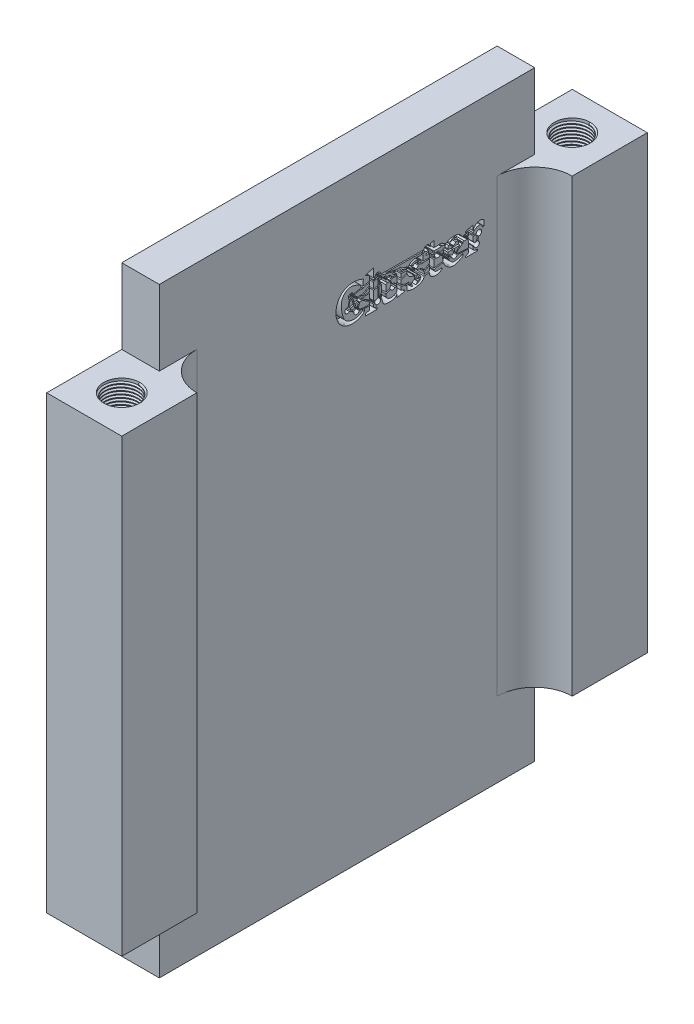
SolidWorks part; units mm, degrees
material "Polylactic Acid (PLA)"
ref_plane "Front Plane" through (0, 0, 0) normal (0, 0, 1) x (1, 0, 0)
ref_plane "Top Plane" through (0, 0, 0) normal (0, 1, 0) x (1, 0, 0)
ref_plane "Right Plane" through (0, 0, 0) normal (1, 0, 0) x (0, 0, -1)
sketch "Sketch2" plane through (0, 0, 0) normal (1, 0, 0) x (0, 0, -1)
  line L0 (-25, 40) -> (25, 40)
  line L1 (-25, 40) -> (-25, 30)
  line L2 (-25, -40) -> (25, -40)
  line L3 (25, 30) -> (35, 30)
  line L4 (25, 40) -> (25, 30)
  line L5 (35, 30) -> (35, -30)
  line L7 (25, -40) -> (25, -30)
  line L8 (25, -30) -> (35, -30)
  line L12 (-25, 30) -> (-35, 30)
  line L13 (-35, 30) -> (-35, -30)
  line L18 (-35, -30) -> (-25, -30)
  line L19 (-25, -30) -> (-25, -40)
extrude "Boss-Extrude1" add sketch "Sketch2" along normal blind 5
sketch "Sketch3" plane through (5, 0, 0) normal (1, 0, 0) x (0, 0, -1)
  line L1 (-35, 30) -> (-25, 30)
  line L2 (-35, 30) -> (-35, -30)
  line L3 (-35, -30) -> (-25, -30)
  line L4 (-25, 30) -> (-25, -30)
  line L5 (25, 30) -> (35, 30)
  line L6 (25, 30) -> (25, -30)
  line L7 (25, -30) -> (35, -30)
  line L8 (35, 30) -> (35, -30)
extrude "Boss-Extrude2" add sketch "Sketch3" along normal blind 5
fillet "Fillet1" radius 5 2 edges at (5, 0, -25) (5, 0, 25)
sketch "Sketch4" plane through (0, -30, 0) normal (0, -1, 0) x (1, 0, 0)
  line L0 (10, 30) -> (0, 30) construction
  line L3 (10, 35) -> (10, 25) construction
  line L5 (0, 35) -> (0, 25) construction
  line L8 (5, 35) -> (5, 25) construction
  line L10 (10, 35) -> (0, 35) construction
  line L11 (10, -30) -> (0, -30) construction
  line L12 (10, -25) -> (10, -35) construction
  line L13 (0, -25) -> (0, -35) construction
  line L14 (5, -35) -> (5, -25) construction
  line L15 (10, -35) -> (0, -35) construction
  circle A0 centre (5, 30) radius 2.4
  circle A1 centre (5, -30) radius 2.4
extrude "Cut-Extrude1" cut sketch "Sketch4" against normal blind 100
sketch "Sketch5" plane through (5, 0, 0) normal (1, 0, 0) x (0, 0, -1)
  line L2 (-1.6758, 24.7708) -> (8.3242, 24.7708) construction
  line L3 (2.4536, 27.3276) -> (3.5353, 27.6605)
  line L4 (2.3077, 23.2222) -> (2.3077, 23.5824)
  line L5 (1.7345, 26.5976) -> (1.8851, 26.16)
  line L6 (2.1172, 25.9583) -> (1.9546, 25.9583)
  line L7 (1.9299, 26.03) -> (1.9546, 25.9583)
  line L8 (3.5353, 23.0892) -> (3.5353, 23.4603)
  line L9 (3.5353, 23.0892) -> (4.0093, 22.8719)
  line L10 (4.0093, 22.8719) -> (4.0093, 22.6248)
  line L11 (4.0093, 22.6248) -> (2.4536, 22.6248)
  line L12 (2.4536, 22.6248) -> (2.4536, 22.8719)
  line L13 (2.4536, 22.8719) -> (2.9944, 23.0384)
  line L14 (2.9944, 23.0384) -> (2.9944, 23.5425)
  line L15 (2.9944, 27.0164) -> (2.4536, 27.3276)
  line L16 (4.1073, 25.7038) -> (4.1453, 25.7127)
  line L17 (5.1882, 25.9583) -> (5.1882, 25.6207)
  line L18 (4.1073, 25.5701) -> (4.1453, 25.5537)
  line L19 (4.1073, 25.5701) -> (4.1073, 25.7038)
  line L20 (4.5926, 25.204) -> (4.5926, 24.2573)
  line L21 (6.0972, 25.7038) -> (6.5089, 25.7983)
  line L22 (7.2057, 25.9583) -> (7.2057, 25.7756)
  line L23 (7.2057, 23.2222) -> (7.6797, 23.0384)
  line L24 (7.6797, 23.0384) -> (7.6797, 22.8719)
  line L25 (7.6797, 22.8719) -> (6.6515, 22.6358)
  line L26 (6.6515, 22.6358) -> (6.6515, 23.0622)
  line L27 (6.0972, 25.5701) -> (6.0972, 25.7038)
  line L28 (6.5373, 25.4364) -> (6.0972, 25.5701)
  line L29 (6.6515, 25.3609) -> (6.6515, 25.3215)
  line L30 (6.6515, 25.3609) -> (6.5373, 25.4364)
  line L31 (10.1325, 25.854) -> (10.1325, 25.1438)
  line L32 (9.9531, 24.9048) -> (10.1325, 24.9048)
  line L33 (7.9697, 23.6741) -> (7.9697, 23.6079)
  line L34 (7.9697, 23.6741) -> (8.1889, 23.6741)
  line L35 (11.0797, 26.6948) -> (11.5721, 26.7808)
  line L36 (11.5721, 26.7808) -> (11.5721, 25.9583)
  line L37 (11.5721, 25.9583) -> (12.7046, 25.9583)
  line L38 (2.1172, 27.0472) -> (2.1774, 27.0164)
  line L39 (12.7046, 25.9583) -> (12.6715, 25.854)
  line L40 (12.5815, 25.5701) -> (11.5721, 25.5701)
  line L41 (11.5721, 25.5701) -> (11.5721, 25.4364)
  line L42 (12.639, 23.0892) -> (12.639, 22.9525)
  line L43 (10.4888, 25.7756) -> (10.4888, 25.5701)
  line L44 (10.4888, 25.5701) -> (10.9894, 25.5701)
  line L45 (10.9894, 25.5701) -> (10.9894, 25.0862)
  line L46 (13.4186, 24.9048) -> (13.4186, 24.7498)
  line L47 (13.4186, 24.7498) -> (14.0346, 24.7498)
  line L48 (13.4186, 24.5085) -> (14.0612, 24.5085)
  line L49 (15.4703, 24.5085) -> (15.4703, 24.612)
  line L50 (14.2741, 24.5085) -> (15.0602, 24.5085)
  line L51 (13.4186, 24.5085) -> (13.4186, 24.2032)
  line L52 (15.4703, 23.3904) -> (15.4703, 23.0892)
  line L53 (16.8079, 25.2832) -> (16.8079, 25.9583)
  line L54 (16.8079, 25.9583) -> (15.7575, 25.7038)
  line L55 (15.7575, 25.7038) -> (15.7575, 25.5701)
  line L56 (15.7575, 25.5701) -> (16.0776, 25.5172)
  line L57 (16.0776, 25.5172) -> (16.2129, 25.3283)
  line L58 (16.2129, 25.3283) -> (16.2129, 24.977)
  line L59 (16.2129, 23.0892) -> (16.0776, 22.9538)
  line L60 (16.0776, 22.9538) -> (15.7575, 22.8763)
  line L61 (15.7575, 22.8763) -> (15.7575, 22.6899)
  line L62 (15.7575, 22.6899) -> (17.407, 22.6899)
  line L63 (17.407, 22.6899) -> (17.407, 22.8763)
  line L64 (17.407, 22.8763) -> (16.9374, 22.9538)
  line L65 (16.9374, 22.9538) -> (16.8079, 23.0833)
  line L66 (16.8079, 25.0616) -> (16.8079, 24.8345)
  line L67 (18.2441, 25.854) -> (18.2441, 25.1109)
  line L68 (18.2441, 25.1109) -> (18.1374, 25.1109)
  line L69 (18.1374, 25.1109) -> (18.0307, 25.1109)
  line L70 (0.3215, 25.5545) -> (0.159, 24.825)
  line L71 (0.2345, 24.7992) -> (0.4327, 25.5015)
  line L72 (0.4196, 24.3322) -> (1.0203, 24.0079)
  line L73 (0.9372, 23.8682) -> (0.3328, 24.2032)
  line L74 (1.5168, 24.0398) -> (1.6909, 24.6311)
  line L75 (1.3686, 24.1124) -> (1.5168, 24.7002)
  line L76 (1.4977, 25.274) -> (0.89, 25.7756)
  line L77 (1.3979, 25.1389) -> (0.8146, 25.6207)
  line L78 (0.6074, 25.4956) -> (0.8281, 24.8629)
  line L79 (0.89, 24.6854) -> (1.1034, 24.0733)
  line L80 (1.3745, 25.0616) -> (0.9855, 24.9143)
  line L81 (1.3928, 24.8629) -> (1.0537, 24.7344)
  line L82 (0.8281, 24.8629) -> (0.362, 24.7004)
  line L83 (0.89, 24.6854) -> (0.4404, 24.5287)
  line L84 (0.8833, 25.9583) -> (1.8851, 26.16)
  line L85 (0.8977, 25.831) -> (1.9299, 26.03)
  line L86 (2.1816, 23.7185) -> (1.6512, 23.7787)
  line L87 (1.6427, 23.6741) -> (2.1816, 23.5824)
  line L88 (2.1816, 23.7185) -> (2.9944, 23.6741)
  line L89 (2.3077, 23.5824) -> (2.9944, 23.5425)
  line L90 (3.5353, 23.6201) -> (3.7437, 23.5775)
  line L91 (3.5353, 23.4603) -> (3.7489, 23.4282)
  line L92 (2.0442, 24.7992) -> (2.9944, 24.1994)
  line L93 (1.9546, 24.702) -> (2.9944, 24.0398)
  line L94 (3.5353, 23.8682) -> (3.7986, 23.7002)
  line L95 (3.5353, 23.7002) -> (3.7485, 23.5983)
  line L96 (2.0946, 25.0616) -> (2.9944, 25.1389)
  line L97 (2.0895, 24.9048) -> (2.9944, 24.9947)
  line L98 (1.9714, 25.274) -> (2.9944, 25.8884)
  line L99 (2.0712, 25.1389) -> (2.9944, 25.6654)
  line L100 (2.1172, 26.2106) -> (2.9944, 26.3781)
  line L101 (2.1172, 26.03) -> (2.9944, 26.242)
  line L102 (3.5353, 26.4822) -> (3.7456, 26.5393)
  line L103 (3.5353, 26.2915) -> (3.7452, 26.4277)
  line L104 (3.5353, 26.16) -> (3.777, 26.3241)
  line L105 (3.5353, 25.9873) -> (3.8304, 26.2426)
  line L106 (4.1453, 26.118) -> (4.1453, 25.7127)
  line L107 (4.2814, 26.16) -> (4.2814, 25.7448)
  line L108 (3.5353, 25.2269) -> (4.1453, 25.3042)
  line L109 (4.2814, 25.3215) -> (4.5926, 25.3609)
  line L110 (4.1453, 25.5537) -> (4.1453, 25.3042)
  line L111 (4.2814, 25.4951) -> (4.2814, 25.3215)
  line L112 (4.1453, 25.1438) -> (4.1073, 23.8694)
  line L113 (4.2814, 25.1621) -> (4.2373, 23.8456)
  line L114 (4.2814, 23.8254) -> (4.5926, 24.2573)
  line L115 (4.3726, 23.7557) -> (4.5926, 24.0079)
  line L116 (4.4161, 23.7002) -> (4.5926, 23.7557)
  line L117 (4.4528, 23.6248) -> (4.5926, 23.6741)
  line L118 (4.3247, 26.1875) -> (4.6748, 25.8374)
  line L119 (4.4161, 26.2852) -> (4.8436, 25.8772)
  line L120 (5.3579, 25.0616) -> (5.1882, 24.8629)
  line L121 (5.2281, 25.2269) -> (5.1882, 25.187)
  line L122 (5.1882, 25.6207) -> (5.2664, 25.5674)
  line L123 (5.2105, 25.4364) -> (5.1882, 25.4364)
  line L124 (5.7799, 25.0616) -> (6.0276, 24.5628)
  line L125 (5.6863, 25.0141) -> (5.8949, 24.5085)
  line L126 (5.9329, 25.3215) -> (6.6515, 25.3215)
  line L127 (5.8949, 25.1943) -> (6.6515, 25.1943)
  line L128 (5.2105, 26.2589) -> (6.7899, 25.8628)
  line L129 (4.4376, 26.3241) -> (6.5089, 25.7983)
  line L130 (5.731, 24.2032) -> (5.1882, 24.0079)
  line L131 (5.7695, 24.0398) -> (5.1882, 23.8254)
  line L132 (6.4596, 24.1504) -> (6.6515, 24.0733)
  line L133 (6.3778, 23.9679) -> (6.6515, 23.9113)
  line L134 (6.44, 24.3322) -> (6.6515, 24.4118)
  line L135 (6.4596, 24.1504) -> (6.6515, 24.2032)
  line L136 (4.4695, 26.4277) -> (10.27, 26.3781)
  line L137 (10.1767, 26.2118) -> (5.2105, 26.2589)
  line L138 (7.2057, 25.7756) -> (8.171, 25.4364)
  line L139 (7.2057, 25.5701) -> (8.0958, 25.3007)
  line L140 (7.2057, 25.3007) -> (8.0958, 25.3007)
  line L141 (7.2057, 25.1438) -> (8.0302, 25.1109)
  line L142 (7.2057, 24.5903) -> (8.0111, 24.824)
  line L143 (7.2057, 24.3865) -> (8.0379, 24.676)
  line L144 (7.2057, 23.8682) -> (7.9697, 23.6079)
  line L145 (7.2057, 23.7002) -> (7.9697, 23.4282)
  line L146 (8.2012, 23.5425) -> (8.6672, 23.3523)
  line L147 (8.2594, 23.3523) -> (8.64, 23.214)
  line L148 (9.0062, 24.0079) -> (9.0062, 23.5802)
  line L149 (9.1649, 23.9581) -> (9.1649, 23.544)
  line L150 (9.1998, 24.612) -> (9.1998, 24.7052)
  line L151 (9.0062, 24.7122) -> (9.0062, 24.676)
  line L152 (9.3032, 23.4282) -> (9.7014, 23.7155)
  line L153 (9.4808, 23.3904) -> (9.7889, 23.5802)
  line L154 (9.4808, 23.3904) -> (9.8335, 23.4073)
  line L155 (9.3725, 23.214) -> (9.8018, 23.2598)
  line L156 (8.8243, 25.2832) -> (8.5542, 25.3609)
  line L157 (8.753, 25.1109) -> (8.5237, 25.1109)
  line L158 (8.753, 25.1109) -> (8.5305, 25.0616)
  line L159 (8.5924, 24.9048) -> (8.7651, 24.9565)
  line L160 (9.3032, 25.3763) -> (9.507, 25.5801)
  line L161 (9.4075, 25.2832) -> (9.6355, 25.5112)
  line L162 (9.4728, 25.1438) -> (9.9195, 25.1438)
  line L163 (9.4759, 24.9947) -> (9.9494, 24.9947)
  line L164 (9.8335, 25.9147) -> (10.1767, 26.2118)
  line L165 (10.0487, 25.8716) -> (10.3588, 26.139)
  line L166 (10.8253, 26.0645) -> (10.9077, 25.9278)
  line L167 (11.0024, 26.3781) -> (11.0912, 26.3241)
  line L168 (10.1325, 25.1438) -> (10.9894, 25.0862)
  line L169 (10.1325, 24.9565) -> (10.9894, 24.9565)
  line L170 (10.2373, 24.0079) -> (10.9894, 24.4436)
  line L171 (10.2799, 23.8254) -> (10.9894, 24.2573)
  line L172 (10.3021, 23.5032) -> (10.9894, 23.544)
  line L173 (10.2859, 23.3149) -> (10.9894, 23.3904)
  line L174 (11.5721, 25.4364) -> (11.8265, 25.1697)
  line L175 (11.5721, 25.271) -> (11.7597, 25.0834)
  line L176 (11.5721, 25.0616) -> (11.7484, 25.0616)
  line L177 (11.5721, 24.9048) -> (11.7132, 24.9048)
  line L178 (11.5721, 24.7498) -> (11.7156, 24.8629)
  line L179 (11.5721, 24.5903) -> (11.7681, 24.7118)
  line L180 (11.5721, 23.6079) -> (12.8026, 23.7558)
  line L181 (11.5721, 23.4282) -> (12.8468, 23.6081)
  line L182 (12.6715, 25.854) -> (13.249, 25.6326)
  line L183 (12.6117, 25.6654) -> (13.1369, 25.4989)
  line L184 (13.0086, 25.3005) -> (12.4103, 25.0616)
  line L185 (12.8934, 25.0616) -> (12.4456, 24.9048)
  line L186 (12.7605, 24.4158) -> (12.3769, 24.6912)
  line L187 (12.7815, 24.592) -> (12.43, 24.7992)
  line L188 (13.769, 25.2269) -> (13.5317, 25.2269)
  line L189 (13.8334, 25.4823) -> (13.7071, 25.5172)
  line L190 (14.0346, 24.7498) -> (14.0047, 24.9279)
  line L191 (14.2228, 24.7498) -> (14.167, 24.9064)
  line L192 (14.7521, 25.3609) -> (14.4876, 25.3609)
  line L193 (14.8219, 25.1668) -> (14.4836, 25.1668)
  line L194 (15.5065, 25.3283) -> (15.3453, 25.3283)
  line L195 (15.4703, 24.612) -> (15.5928, 24.7345)
  line L196 (13.955, 23.6741) -> (13.5151, 23.6741)
  line L197 (14.0047, 23.8582) -> (13.4186, 24.2032)
  line L198 (13.4628, 23.8254) -> (13.769, 23.8254)
  line L199 (13.769, 23.8254) -> (13.4246, 24.0282)
  line L200 (14.0612, 24.5085) -> (14.2123, 24.0237)
  line L201 (14.2741, 24.5085) -> (14.3503, 24.0391)
  line L202 (14.528, 23.9763) -> (15.0602, 24.5085)
  line L203 (14.6086, 23.9011) -> (15.3455, 24.5085)
  line L204 (14.6851, 23.7155) -> (16.2129, 23.6201)
  line L205 (14.6752, 23.5802) -> (16.2129, 23.4842)
  line L206 (16.1175, 24.9947) -> (16.2129, 24.977)
  line L207 (16.0447, 24.8345) -> (16.2129, 24.7744)
  line L208 (16.0447, 24.8345) -> (16.2129, 24.6662)
  line L209 (15.9504, 24.7503) -> (16.2129, 24.4118)
  line L210 (16.8079, 24.0237) -> (17.0224, 23.7787)
  line L211 (16.8079, 23.4842) -> (16.8979, 23.4842)
  line L212 (16.8079, 24.8345) -> (17.2133, 24.7504)
  line L213 (16.8079, 24.676) -> (17.2113, 24.612)
  line L214 (17.355, 24.3809) -> (17.2396, 23.8686)
  line L215 (17.5124, 24.3147) -> (17.407, 23.8402)
  line L216 (1.2857, 24.1219) -> (1.0537, 24.7344)
  line L217 (0.9855, 24.9143) -> (0.743, 25.5545)
  line L218 (4.5926, 24.0079) -> (4.5926, 23.7557)
  line L219 (2.9944, 23.6741) -> (2.9944, 24.0398)
  line L220 (2.9944, 24.1994) -> (2.9944, 24.9947)
  line L221 (2.9944, 25.1389) -> (2.9944, 25.6654)
  line L222 (2.9944, 25.8884) -> (2.9944, 26.242)
  line L223 (2.9944, 26.3781) -> (2.9944, 27.0164)
  line L224 (2.1172, 25.9583) -> (2.1172, 26.03)
  line L225 (2.1172, 26.2106) -> (2.1774, 27.0164)
  line L226 (3.5353, 23.6201) -> (3.5353, 23.7002)
  line L227 (3.5353, 23.8682) -> (3.5353, 25.0616)
  line L228 (3.5353, 25.2269) -> (3.5353, 25.9873)
  line L229 (3.5353, 26.16) -> (3.5353, 26.2915)
  line L230 (3.5353, 26.4822) -> (3.5353, 27.6605)
  line L231 (4.2814, 25.7448) -> (4.6748, 25.8374)
  line L232 (4.8436, 25.8772) -> (5.1882, 25.9583)
  line L233 (4.2814, 25.4951) -> (4.5926, 25.3609)
  line L234 (4.5926, 25.204) -> (4.2814, 25.1621)
  line L235 (4.1453, 25.1438) -> (3.5353, 25.0616)
  line L236 (5.1882, 25.4364) -> (5.1882, 25.187)
  line L237 (5.1882, 24.8629) -> (5.1882, 24.0079)
  line L238 (5.1882, 23.8254) -> (5.1882, 23.6741)
  line L239 (6.6515, 25.1943) -> (6.6515, 24.4118)
  line L240 (6.6515, 24.0733) -> (6.6515, 24.2032)
  line L241 (6.6515, 23.9113) -> (6.6515, 23.3904)
  line L242 (6.7899, 25.8628) -> (7.2057, 25.9583)
  line L243 (7.2057, 25.5701) -> (7.2057, 25.3007)
  line L244 (7.2057, 25.1438) -> (7.2057, 24.5903)
  line L245 (7.2057, 24.3865) -> (7.2057, 23.8682)
  line L246 (7.2057, 23.7002) -> (7.2057, 23.2222)
  line L247 (10.0487, 25.8716) -> (10.1325, 25.854)
  line L248 (8.5305, 25.0616) -> (8.5237, 25.1109)
  line L249 (9.9494, 24.9947) -> (9.9531, 24.9048)
  line L250 (7.9697, 23.4282) -> (7.9697, 22.7539)
  line L251 (10.1325, 24.9565) -> (10.1325, 24.9048)
  line L252 (10.9894, 24.9565) -> (10.9894, 24.4436)
  line L253 (10.9894, 24.2573) -> (10.9894, 23.544)
  line L254 (10.9894, 23.3904) -> (10.9894, 23.1495)
  line L255 (11.5721, 25.271) -> (11.5721, 25.0616)
  line L256 (11.5721, 25.0616) -> (11.5733, 25.0552)
  line L257 (11.5721, 24.9048) -> (11.5721, 24.7498)
  line L258 (11.5721, 23.6079) -> (11.5721, 24.5903)
  line L259 (11.5721, 23.3095) -> (11.5721, 23.4282)
  line L260 (12.5815, 25.5701) -> (12.6117, 25.6654)
  line L261 (14.2228, 24.7498) -> (14.8219, 24.7498)
  line L262 (15.3455, 24.5085) -> (15.4703, 24.5085)
  line L263 (13.4186, 24.5085) -> (13.4186, 24.2032)
  line L264 (16.2129, 24.7744) -> (16.2129, 24.6662)
  line L265 (16.2129, 24.4118) -> (16.2129, 23.6201)
  line L266 (16.2129, 23.4842) -> (16.2129, 23.0892)
  line L267 (16.8079, 24.676) -> (16.8079, 24.0237)
  line L268 (16.8079, 23.4842) -> (16.8079, 23.0833)
  arc A0 (0.743, 25.5545) -> (0.8146, 25.6207) centre (0.5322, 25.854) ccw
  arc A1 (0.362, 24.7004) -> (0.2345, 24.7992) centre (0.0793, 24.4675) ccw
  arc A2 (2.0712, 25.1389) -> (2.0946, 25.0616) centre (1.7345, 24.9947) cw
  arc A3 (1.6512, 23.7787) -> (1.5168, 24.0398) centre (1.2857, 23.7557) ccw
  arc A4 (3.7456, 26.5393) -> (4.4691, 26.4252) centre (4.1073, 26.4822) cw
  arc A5 (4.2373, 23.8456) -> (4.2814, 23.8254) centre (4.1073, 23.5032) cw
  arc A6 (5.8949, 25.1943) -> (5.7799, 25.0616) centre (5.5689, 25.3609) cw
  arc A7 (6.3778, 23.9679) -> (5.7695, 24.0398) centre (6.0972, 24.2032) cw
  arc A8 (8.64, 23.214) -> (8.8339, 22.8909) centre (9.0062, 23.214) ccw
  arc A9 (9.4759, 24.9947) -> (9.1998, 24.7052) centre (9.1159, 25.0616) cw
  arc A10 (10.27, 26.3781) -> (11.0024, 26.3781) centre (10.6362, 26.3781) cw
  arc A11 (12.4456, 24.9048) -> (12.43, 24.7992) centre (12.0794, 24.9048) cw
  arc A12 (13.8334, 25.4823) -> (14.4876, 25.3609) centre (14.1326, 25.271) cw
  arc A13 (14.3503, 24.0391) -> (14.528, 23.9763) centre (14.3212, 23.6741) cw
  arc A14 (15.5065, 25.3283) -> (16.1175, 24.9947) centre (15.7575, 25.0616) cw
  arc A15 (17.2133, 24.7504) -> (17.5124, 24.3147) centre (17.5719, 24.676) cw
  arc A16 (17.407, 23.8402) -> (16.8979, 23.4842) centre (17.2637, 23.5032) cw
  arc A17 (1.3686, 24.1124) -> (1.2857, 24.1219) centre (1.2857, 23.7557) ccw
  arc A18 (1.1034, 24.0733) -> (1.0203, 24.0079) centre (1.2857, 23.7557) ccw
  arc A19 (0.9372, 23.8682) -> (1.6427, 23.6741) centre (1.2857, 23.7557) ccw
  arc A20 (0.4196, 24.3322) -> (0.4404, 24.5287) centre (0.0793, 24.4675) ccw
  arc A21 (0.3328, 24.2032) -> (0.159, 24.825) centre (0.0793, 24.4675) cw
  arc A22 (0.4327, 25.5015) -> (0.6074, 25.4956) centre (0.5322, 25.854) ccw
  arc A23 (0.89, 25.7756) -> (0.8977, 25.831) centre (0.5322, 25.854) ccw
  arc A24 (0.3215, 25.5545) -> (0.8833, 25.9583) centre (0.5322, 25.854) cw
  arc A25 (1.4977, 25.274) -> (1.9714, 25.274) centre (1.7345, 24.9947) cw
  arc A26 (2.0895, 24.9048) -> (2.0442, 24.7992) centre (1.7345, 24.9947) cw
  arc A27 (1.9546, 24.702) -> (1.6909, 24.6311) centre (1.7345, 24.9947) cw
  arc A28 (1.5168, 24.7002) -> (1.3928, 24.8629) centre (1.7345, 24.9947) cw
  arc A29 (1.3745, 25.0616) -> (1.3979, 25.1389) centre (1.7345, 24.9947) cw
  arc A30 (3.777, 26.3241) -> (3.7452, 26.4277) centre (4.1073, 26.4822) cw
  arc A31 (3.8304, 26.2426) -> (4.1453, 26.118) centre (4.1073, 26.4822) ccw
  arc A32 (4.2814, 26.16) -> (4.3247, 26.1875) centre (4.1073, 26.4822) ccw
  arc A33 (4.4161, 26.2852) -> (4.4376, 26.3241) centre (4.1073, 26.4822) ccw
  arc A34 (3.7986, 23.7002) -> (4.1073, 23.8694) centre (4.1073, 23.5032) cw
  arc A35 (4.3726, 23.7557) -> (4.4161, 23.7002) centre (4.1073, 23.5032) cw
  arc A36 (3.7485, 23.5983) -> (3.7437, 23.5775) centre (4.1073, 23.5032) ccw
  arc A37 (4.4528, 23.6248) -> (3.7489, 23.4282) centre (4.1073, 23.5032) cw
  arc A38 (5.2664, 25.5674) -> (5.9329, 25.3215) centre (5.5689, 25.3609) cw
  arc A39 (5.6863, 25.0141) -> (5.3579, 25.0616) centre (5.5689, 25.3609) cw
  arc A40 (5.2281, 25.2269) -> (5.2105, 25.4364) centre (5.5689, 25.3609) cw
  arc A41 (6.0276, 24.5628) -> (6.44, 24.3322) centre (6.0972, 24.2032) cw
  arc A42 (5.731, 24.2032) -> (5.8949, 24.5085) centre (6.0972, 24.2032) cw
  arc A43 (8.6672, 23.3523) -> (9.0062, 23.5802) centre (9.0062, 23.214) cw
  arc A44 (9.3725, 23.214) -> (9.1615, 22.8823) centre (9.0062, 23.214) cw
  arc A45 (9.3032, 23.4282) -> (9.1649, 23.544) centre (9.0062, 23.214) ccw
  arc A46 (9.4075, 25.2832) -> (9.4728, 25.1438) centre (9.1159, 25.0616) cw
  arc A47 (9.0062, 24.7122) -> (8.7651, 24.9565) centre (9.1159, 25.0616) cw
  arc A48 (8.8243, 25.2832) -> (9.3032, 25.3763) centre (9.1159, 25.0616) cw
  arc A49 (10.8253, 26.0645) -> (10.3588, 26.139) centre (10.6362, 26.3781) cw
  arc A50 (11.8265, 25.1697) -> (12.4103, 25.0616) centre (12.0794, 24.9048) cw
  arc A51 (12.3769, 24.6912) -> (11.7681, 24.7118) centre (12.0794, 24.9048) cw
  arc A52 (11.7156, 24.8629) -> (11.7132, 24.9048) centre (12.0794, 24.9048) cw
  arc A53 (11.7484, 25.0616) -> (11.7597, 25.0834) centre (12.0794, 24.9048) cw
  arc A54 (11.7484, 25.0616) -> (11.7597, 25.0834) centre (12.0794, 24.9048) cw
  arc A55 (15.5928, 24.7345) -> (15.9504, 24.7503) centre (15.7575, 25.0616) ccw
  arc A56 (14.0047, 24.9279) -> (13.769, 25.2269) centre (14.1326, 25.271) cw
  arc A57 (14.4836, 25.1668) -> (14.167, 24.9064) centre (14.1326, 25.271) cw
  arc A58 (14.6086, 23.9011) -> (14.6851, 23.7155) centre (14.3212, 23.6741) cw
  arc A59 (14.0047, 23.8582) -> (14.2123, 24.0237) centre (14.3212, 23.6741) cw
  arc A60 (14.6752, 23.5802) -> (13.955, 23.6741) centre (14.3212, 23.6741) cw
  arc A61 (17.2113, 24.612) -> (17.355, 24.3809) centre (17.5719, 24.676) ccw
  arc A62 (17.0224, 23.7787) -> (17.2396, 23.8686) centre (17.2637, 23.5032) cw
  spline S0 degree 3 poles (2.1172, 27.0472) (1.3409, 27.4346) (-0.6003, 27.4669) (-1.781, 25.1158) (-0.8503, 22.383) (1.5656, 22.4435) (2.3077, 23.2222) knots 0 0 0 0 0.267187 0.468549 0.685025 1 1 1 1
  spline S1 degree 3 poles (2.1816, 23.5824) (1.7136, 22.8646) (-0.2511, 22.8228) (-0.7573, 24.7761) (-0.8506, 26.2693) (0.4526, 27.2045) (1.3052, 26.7686) (1.7345, 26.5976) knots 0 0 0 0 0.311244 0.483795 0.695631 0.819108 1 1 1 1
  spline S2 degree 3 poles (6.6515, 23.0622) (6.4288, 22.707) (5.814, 22.5922) (4.6667, 22.689) (4.7006, 23.447) (4.5926, 23.6741) knots 0 0 0 0 0.389848 0.700971 1 1 1 1
  spline S3 degree 3 poles (5.1882, 23.6741) (5.182, 22.9279) (6.3158, 22.84) (6.6515, 23.3904) knots 0 0 0 0 1 1 1 1
  spline S4 degree 3 poles (7.9697, 22.7539) (8.2433, 22.663) (8.7213, 22.4904) (9.3375, 22.6168) (9.8954, 22.7739) (10.2598, 23.0251) (10.2859, 23.3149) knots 0 0 0 0 0.333928 0.549389 0.698568 1 1 1 1
  spline S5 degree 2 poles (11.0797, 26.6948) (11.1276, 26.5115) (11.0912, 26.3241) knots 0 0 0 1 1 1
  spline S6 degree 2 poles (12.7815, 24.592) (12.8156, 24.8313) (12.8934, 25.0616) knots 0 0 0 1 1 1
  spline S7 degree 3 poles (11.5721, 23.3095) (11.8198, 22.918) (12.268, 23.1173) (12.639, 23.0892) knots 0 0 0 0 1 1 1 1
  spline S8 degree 3 poles (12.639, 22.9525) (12.404, 22.7562) (11.7745, 22.4926) (11.0953, 22.8048) (10.9894, 23.1495) knots 0 0 0 0 0.479275 1 1 1 1
  spline S9 degree 2 poles (13.4186, 24.9048) (13.4642, 25.0697) (13.5317, 25.2269) knots 0 0 0 1 1 1
  spline S10 degree 2 poles (13.4246, 24.0282) (13.4353, 23.9251) (13.4628, 23.8254) knots 0 0 0 1 1 1
  spline S11 degree 3 poles (16.8079, 25.2832) (16.9244, 25.8843) (17.7562, 26.2798) (18.2441, 25.854) knots 0 0 0 0 1 1 1 1
  spline S12 degree 3 poles (16.8079, 25.0616) (16.9631, 25.4575) (17.9901, 25.8442) (18.0307, 25.1109) knots 0 0 0 0 1 1 1 1
  spline S13 degree 1 poles (8.1889, 23.6741) (8.2012, 23.5425) knots 0 0 1 1
  spline S14 degree 2 poles (8.2594, 23.3523) (8.4185, 23.0007) (8.8339, 22.8909) knots 0 0 0 1 1 1
  spline S15 degree 2 poles (9.1615, 22.8823) (9.5723, 22.9245) (9.8018, 23.2598) knots 0 0 0 1 1 1
  spline S16 degree 2 poles (9.8335, 23.4073) (9.8293, 23.4982) (9.7889, 23.5802) knots 0 0 0 1 1 1
  spline S17 degree 2 poles (9.7014, 23.7155) (9.4916, 23.9525) (9.1649, 23.9581) knots 0 0 0 1 1 1
  spline S18 degree 3 poles (9.0062, 24.0079) (8.6229, 24.1123) (8.136, 24.2349) (8.0379, 24.676) knots 0 0 0 0 1 1 1 1
  spline S19 degree 2 poles (8.0111, 24.824) (7.9973, 24.9693) (8.0302, 25.1109) knots 0 0 0 1 1 1
  spline S20 degree 3 poles (8.171, 25.4364) (8.5147, 26.0188) (9.25, 26.033) (9.8335, 25.9147) knots 0 0 0 0 1 1 1 1
  spline S21 degree 2 poles (10.3021, 23.5032) (10.3032, 23.6652) (10.2799, 23.8254) knots 0 0 0 1 1 1
  spline S22 degree 3 poles (10.2373, 24.0079) (10.1121, 24.4408) (9.5537, 24.4604) (9.1998, 24.612) knots 0 0 0 0 1 1 1 1
  spline S23 degree 2 poles (9.0062, 24.676) (8.7614, 24.7237) (8.5924, 24.9048) knots 0 0 0 1 1 1
  spline S24 degree 3 poles (8.5542, 25.3609) (8.6622, 25.7373) (9.2311, 25.7064) (9.507, 25.5801) knots 0 0 0 0 1 1 1 1
  spline S25 degree 2 poles (9.6355, 25.5112) (9.8366, 25.3816) (9.9195, 25.1438) knots 0 0 0 1 1 1
  spline S26 degree 2 poles (10.4888, 25.7756) (10.7506, 25.7512) (10.9077, 25.9278) knots 0 0 0 1 1 1
  spline S27 degree 2 poles (13.0086, 25.3005) (13.0668, 25.4036) (13.1369, 25.4989) knots 0 0 0 1 1 1
  spline S28 degree 3 poles (13.249, 25.6326) (13.4903, 25.8994) (14.0766, 25.9919) (14.8943, 25.9154) (15.2304, 25.5457) (15.3453, 25.3283) knots 0 0 0 0 0.435858 0.689114 1 1 1 1
  spline S29 degree 2 poles (12.7605, 24.4158) (12.7228, 24.0786) (12.8026, 23.7558) knots 0 0 0 1 1 1
  spline S30 degree 3 poles (12.8468, 23.6081) (12.9881, 23.0435) (14.1108, 22.1477) (15.0789, 22.8869) (15.4703, 23.0892) knots 0 0 0 0 0.572485 1 1 1 1
  spline S31 degree 3 poles (13.7071, 25.5172) (13.8246, 25.6622) (14.2687, 25.9356) (14.6616, 25.5563) (14.7521, 25.3609) knots 0 0 0 0 0.460627 1 1 1 1
  spline S32 degree 2 poles (14.8219, 25.1668) (14.8219, 24.9583) (14.8219, 24.7498) knots 0 0 0 1 1 1
  spline S33 degree 3 poles (13.5151, 23.6741) (13.6253, 23.4159) (14.2092, 22.6886) (15.1228, 23.2126) (15.4703, 23.3904) knots 0 0 0 0 0.391189 1 1 1 1
extrude "Cut-Extrude2" cut sketch "Sketch5" against normal blind 1.5 contours S33 L196 A60 L205 L266 L59 L60 L61 L62 L63 L64 L65 L268 L211 A16 L215 A15 L212 L66 S12 L69 L68 L67 S11 L53 L54 L55 L56 L57 L58 L206 A14 L194 S28 L182 L39 L37 L36 L35 S5 L167 A10 L136 A4 L102 L230 L3 L15 L223 region at (5, 27.2994, -3.0543)
thread "Thread1" pitch 0.4 method extrude profile "Thread Profile1" start angle 90, offset 0, length 10, pitch 0.4, diameter 4.8
ref_plane "Plane1" through (5, 30, 27.6) normal (-1, 0, 0) x (0, 0, -1)
sketch "Thread Profile1" plane through (5, 30, 27.6) normal (-1, 0, 0) x (0, 0, -1)
  line L0 (0, 0) -> (0, 0.4) construction
  line L11 (0, 0) -> (0, 0.35)
  line L12 (0, 0.35) -> (-0.2165, 0.225)
  line L13 (-0.2165, 0.225) -> (-0.2165, 0.125)
  line L15 (-0.2165, 0.125) -> (0, 0)
  line L17 (-0.2165, 0.175) -> (0, 0.175) construction
  point P2 (0, 0)
  dimension "Pitch" = 0.4
  dimension "Profile_Angle" = 60
  dimension "Profile_Land" = 0.1
  dimension "Profile_Height" = 0.2165
thread "Thread2" pitch 0.4 method extrude profile "Thread Profile2" start angle 90, offset 0, length 10, pitch 0.4, diameter 4.8
ref_plane "Plane2" through (5, 30, -32.4) normal (-1, 0, 0) x (0, 0, -1)
sketch "Thread Profile2" plane through (5, 30, -32.4) normal (-1, 0, 0) x (0, 0, -1)
  line L0 (0, 0) -> (0, 0.4) construction
  line L11 (0, 0) -> (0, 0.35)
  line L12 (0, 0.35) -> (-0.2165, 0.225)
  line L13 (-0.2165, 0.225) -> (-0.2165, 0.125)
  line L15 (-0.2165, 0.125) -> (0, 0)
  line L17 (-0.2165, 0.175) -> (0, 0.175) construction
  point P2 (0, 0)
  dimension "Pitch" = 0.4
  dimension "Profile_Angle" = 60
  dimension "Profile_Land" = 0.1
  dimension "Profile_Height" = 0.2165
thread "Thread3" pitch 0.4 method extrude profile "Thread Profile3" start angle 90, offset 0, length 10, pitch 0.4, diameter 4.8
ref_plane "Plane3" through (5, -30, 27.6) normal (1, 0, 0) x (0, 0, -1)
sketch "Thread Profile3" plane through (5, -30, 27.6) normal (1, 0, 0) x (0, 0, -1)
  line L0 (0, 0) -> (0, 0.4) construction
  line L11 (0, 0) -> (0, 0.35)
  line L12 (0, 0.35) -> (-0.2165, 0.225)
  line L13 (-0.2165, 0.225) -> (-0.2165, 0.125)
  line L15 (-0.2165, 0.125) -> (0, 0)
  line L17 (-0.2165, 0.175) -> (0, 0.175) construction
  point P2 (0, 0)
  dimension "Pitch" = 0.4
  dimension "Profile_Angle" = 60
  dimension "Profile_Land" = 0.1
  dimension "Profile_Height" = 0.2165
thread "Thread4" pitch 0.4 method extrude profile "Thread Profile4" start angle 90, offset 0, length 10, pitch 0.4, diameter 4.8
ref_plane "Plane4" through (5, -30, -32.4) normal (1, 0, 0) x (0, 0, -1)
sketch "Thread Profile4" plane through (5, -30, -32.4) normal (1, 0, 0) x (0, 0, -1)
  line L0 (0, 0) -> (0, 0.4) construction
  line L11 (0, 0) -> (0, 0.35)
  line L12 (0, 0.35) -> (-0.2165, 0.225)
  line L13 (-0.2165, 0.225) -> (-0.2165, 0.125)
  line L15 (-0.2165, 0.125) -> (0, 0)
  line L17 (-0.2165, 0.175) -> (0, 0.175) construction
  point P2 (0, 0)
  dimension "Pitch" = 0.4
  dimension "Profile_Angle" = 60
  dimension "Profile_Land" = 0.1
  dimension "Profile_Height" = 0.2165
